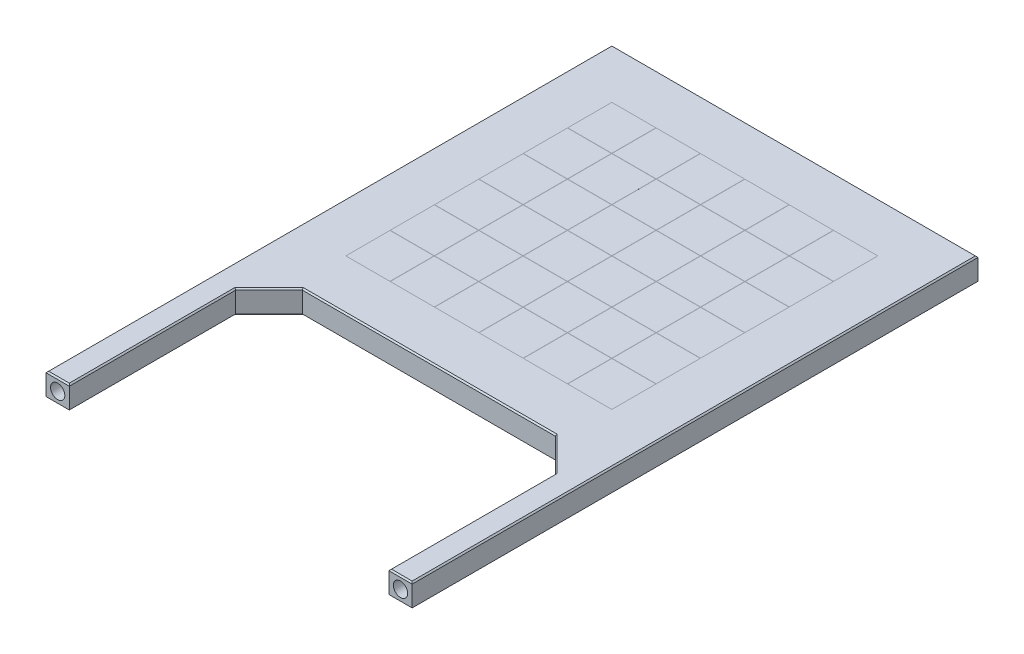
SolidWorks part; units mm, degrees
note: The reader was unsure of these and kept them because the rebuilt part matched: shared geometry of "Sketch7<2>", "Sketch7<3>", "Sketch7<4>".
ref_plane "Front Plane" through (0, 0, 0) normal (0, 0, 1) x (1, 0, 0)
ref_plane "Top Plane" through (0, 0, 0) normal (0, 1, 0) x (1, 0, 0)
ref_plane "Right Plane" through (0, 0, 0) normal (1, 0, 0) x (0, 0, -1)
sketch "Sketch1" plane through (0, 0, 0) normal (0, 1, 0) x (1, 0, 0)
  line L1 (-55, -55) -> (55, -55)
  line L2 (-55, -55) -> (-55, 55)
  line L3 (-55, 55) -> (55, 55)
  line L4 (55, -55) -> (55, 55)
  line L5 (-55, -55) -> (55, 55) construction
  line L6 (-55, 55) -> (55, -55) construction
  point P0 (0, 0)
  dimension "D1" = 110
extrude "Boss-Extrude1" add sketch "Sketch1" along normal blind 7
sketch "Sketch2" plane through (0, 7, 0) normal (0, 1, 0) x (1, 0, 0)
  line L1 (-55, -55) -> (-48, -55)
  line L2 (-55, -55) -> (-55, -115)
  line L3 (-55, -115) -> (-48, -115)
  line L4 (-48, -55) -> (-48, -115)
  line L5 (55, -55) -> (48, -55)
  line L6 (55, -55) -> (55, -115)
  line L7 (55, -115) -> (48, -115)
  line L8 (48, -55) -> (48, -115)
  dimension "D1" = 7
  dimension "D2" = 60
extrude "Boss-Extrude3" add sketch "Sketch2" against normal up to surface (7 mm away) up to face at (0, 0, 0)
sketch "Sketch4" plane through (0, 0, 115) normal (0, 0, 1) x (1, 0, 0)
  line L0 (-48, 7) -> (-55, 0) construction
  line L1 (48, 7) -> (55, 0) construction
  circle A0 centre (-51.5, 3.5) radius 2.15
  circle A1 centre (51.5, 3.5) radius 2.15
  dimension "D1" = 4.3
extrude "Cut-Extrude2" cut sketch "Sketch4" against normal blind 10
sketch "Sketch5" plane through (0, 0, 0) normal (0, -1, 0) x (1, 0, 0)
  line L5 (-40, 40) -> (-26.6667, 40)
  line L6 (-40, 40) -> (-40, 26.6667)
  line L7 (-40, 26.6667) -> (-26.6667, 26.6667)
  line L8 (-26.6667, 40) -> (-26.6667, 26.6667)
  line L9 (-26.6667, 40) -> (-13.3333, 40)
  line L10 (-26.6667, 40) -> (-26.6667, 26.6667)
  line L11 (-26.6667, 26.6667) -> (-13.3333, 26.6667)
  line L12 (-13.3333, 40) -> (-13.3333, 26.6667)
  line L13 (-13.3333, 40) -> (0, 40)
  line L14 (-13.3333, 40) -> (-13.3333, 26.6667)
  line L15 (-13.3333, 26.6667) -> (0, 26.6667)
  line L16 (0, 40) -> (0, 26.6667)
  line L17 (0, 40) -> (13.3333, 40)
  line L18 (0, 40) -> (0, 26.6667)
  line L19 (0, 26.6667) -> (13.3333, 26.6667)
  line L20 (13.3333, 40) -> (13.3333, 26.6667)
  line L21 (13.3333, 40) -> (26.6667, 40)
  line L22 (13.3333, 40) -> (13.3333, 26.6667)
  line L23 (13.3333, 26.6667) -> (26.6667, 26.6667)
  line L24 (26.6667, 40) -> (26.6667, 26.6667)
  line L25 (26.6667, 40) -> (40, 40)
  line L26 (26.6667, 40) -> (26.6667, 26.6667)
  line L27 (26.6667, 26.6667) -> (40, 26.6667)
  line L28 (40, 40) -> (40, 26.6667)
  line L29 (-26.6667, 26.6667) -> (-40, 26.6667)
  line L30 (-26.6667, 26.6667) -> (-26.6667, 13.3333)
  line L31 (-26.6667, 13.3333) -> (-40, 13.3333)
  line L32 (-40, 26.6667) -> (-40, 13.3333)
  line L33 (-26.6667, 26.6667) -> (-13.3333, 26.6667)
  line L34 (-26.6667, 26.6667) -> (-26.6667, 13.3333)
  line L35 (-26.6667, 13.3333) -> (-13.3333, 13.3333)
  line L36 (-13.3333, 26.6667) -> (-13.3333, 13.3333)
  line L37 (-13.3333, 13.3333) -> (0, 13.3333)
  line L38 (-13.3333, 13.3333) -> (-13.3333, 26.6667)
  line L39 (-13.3333, 26.6667) -> (0, 26.6667)
  line L40 (0, 13.3333) -> (0, 26.6667)
  line L41 (0, 13.3333) -> (13.3333, 13.3333)
  line L42 (0, 13.3333) -> (0, 26.6667)
  line L43 (0, 26.6667) -> (13.3333, 26.6667)
  line L44 (13.3333, 13.3333) -> (13.3333, 26.6667)
  line L45 (13.3333, 13.3333) -> (26.6667, 13.3333)
  line L46 (13.3333, 13.3333) -> (13.3333, 26.6667)
  line L47 (13.3333, 26.6667) -> (26.6667, 26.6667)
  line L48 (26.6667, 13.3333) -> (26.6667, 26.6667)
  line L49 (26.6667, 13.3333) -> (40, 13.3333)
  line L50 (26.6667, 13.3333) -> (26.6667, 26.6667)
  line L51 (26.6667, 26.6667) -> (40, 26.6667)
  line L52 (40, 13.3333) -> (40, 26.6667)
  line L53 (-40, 13.3333) -> (-26.6667, 13.3333)
  line L54 (-40, 13.3333) -> (-40, 0)
  line L55 (-40, 0) -> (-26.6667, 0)
  line L56 (-26.6667, 13.3333) -> (-26.6667, 0)
  line L57 (-26.6667, 0) -> (-13.3333, 0)
  line L58 (-26.6667, 0) -> (-26.6667, 13.3333)
  line L59 (-26.6667, 13.3333) -> (-13.3333, 13.3333)
  line L60 (-13.3333, 0) -> (-13.3333, 13.3333)
  line L61 (-13.3333, 0) -> (0, 0)
  line L62 (-13.3333, 0) -> (-13.3333, 13.3333)
  line L63 (-13.3333, 13.3333) -> (0, 13.3333)
  line L64 (0, 0) -> (0, 13.3333)
  line L65 (0, 0) -> (13.3333, 0)
  line L66 (0, 0) -> (0, 13.3333)
  line L67 (0, 13.3333) -> (13.3333, 13.3333)
  line L68 (13.3333, 0) -> (13.3333, 13.3333)
  line L69 (13.3333, 0) -> (26.6667, 0)
  line L70 (13.3333, 0) -> (13.3333, 13.3333)
  line L71 (13.3333, 13.3333) -> (26.6667, 13.3333)
  line L72 (26.6667, 0) -> (26.6667, 13.3333)
  line L73 (26.6667, 0) -> (40, 0)
  line L74 (26.6667, 0) -> (26.6667, 13.3333)
  line L75 (26.6667, 13.3333) -> (40, 13.3333)
  line L76 (40, 0) -> (40, 13.3333)
  line L77 (-40, 0) -> (-26.6667, 0)
  line L78 (-40, 0) -> (-40, -13.3333)
  line L79 (-40, -13.3333) -> (-26.6667, -13.3333)
  line L80 (-26.6667, 0) -> (-26.6667, -13.3333)
  line L81 (-26.6667, -13.3333) -> (-13.3333, -13.3333)
  line L82 (-26.6667, -13.3333) -> (-26.6667, 0)
  line L83 (-26.6667, 0) -> (-13.3333, 0)
  line L84 (-13.3333, -13.3333) -> (-13.3333, 0)
  line L85 (-13.3333, -13.3333) -> (0, -13.3333)
  line L86 (-13.3333, -13.3333) -> (-13.3333, 0)
  line L87 (-13.3333, 0) -> (0, 0)
  line L88 (0, -13.3333) -> (0, 0)
  line L89 (0, -13.3333) -> (13.3333, -13.3333)
  line L90 (0, -13.3333) -> (0, 0)
  line L91 (0, 0) -> (13.3333, 0)
  line L92 (13.3333, -13.3333) -> (13.3333, 0)
  line L93 (13.3333, -13.3333) -> (26.6667, -13.3333)
  line L94 (13.3333, -13.3333) -> (13.3333, 0)
  line L95 (13.3333, 0) -> (26.6667, 0)
  line L96 (26.6667, -13.3333) -> (26.6667, 0)
  line L97 (26.6667, -13.3333) -> (40, -13.3333)
  line L98 (26.6667, -13.3333) -> (26.6667, 0)
  line L99 (26.6667, 0) -> (40, 0)
  line L100 (40, -13.3333) -> (40, 0)
  line L101 (-40, -13.3333) -> (-26.6667, -13.3333)
  line L102 (-40, -13.3333) -> (-40, -26.6667)
  line L103 (-40, -26.6667) -> (-26.6667, -26.6667)
  line L104 (-26.6667, -13.3333) -> (-26.6667, -26.6667)
  line L105 (-26.6667, -26.6667) -> (-13.3333, -26.6667)
  line L106 (-26.6667, -26.6667) -> (-26.6667, -13.3333)
  line L107 (-26.6667, -13.3333) -> (-13.3333, -13.3333)
  line L108 (-13.3333, -26.6667) -> (-13.3333, -13.3333)
  line L109 (-13.3333, -26.6667) -> (0, -26.6667)
  line L110 (-13.3333, -26.6667) -> (-13.3333, -13.3333)
  line L111 (-13.3333, -13.3333) -> (0, -13.3333)
  line L112 (0, -26.6667) -> (0, -13.3333)
  line L113 (0, -26.6667) -> (13.3333, -26.6667)
  line L114 (0, -26.6667) -> (0, -13.3333)
  line L115 (0, -13.3333) -> (13.3333, -13.3333)
  line L116 (13.3333, -26.6667) -> (13.3333, -13.3333)
  line L117 (13.3333, -26.6667) -> (26.6667, -26.6667)
  line L118 (13.3333, -26.6667) -> (13.3333, -13.3333)
  line L119 (13.3333, -13.3333) -> (26.6667, -13.3333)
  line L120 (26.6667, -26.6667) -> (26.6667, -13.3333)
  line L121 (26.6667, -26.6667) -> (40, -26.6667)
  line L122 (26.6667, -26.6667) -> (26.6667, -13.3333)
  line L123 (26.6667, -13.3333) -> (40, -13.3333)
  line L124 (40, -26.6667) -> (40, -13.3333)
  line L125 (-40, -26.6667) -> (-26.6667, -26.6667)
  line L126 (-40, -26.6667) -> (-40, -40)
  line L127 (-40, -40) -> (-26.6667, -40)
  line L128 (-26.6667, -26.6667) -> (-26.6667, -40)
  line L129 (-26.6667, -40) -> (-13.3333, -40)
  line L130 (-26.6667, -40) -> (-26.6667, -26.6667)
  line L131 (-26.6667, -26.6667) -> (-13.3333, -26.6667)
  line L132 (-13.3333, -40) -> (-13.3333, -26.6667)
  line L133 (-13.3333, -40) -> (0, -40)
  line L134 (-13.3333, -40) -> (-13.3333, -26.6667)
  line L135 (-13.3333, -26.6667) -> (0, -26.6667)
  line L136 (0, -40) -> (0, -26.6667)
  line L137 (0, -40) -> (13.3333, -40)
  line L138 (0, -40) -> (0, -26.6667)
  line L139 (0, -26.6667) -> (13.3333, -26.6667)
  line L140 (13.3333, -40) -> (13.3333, -26.6667)
  line L141 (13.3333, -40) -> (26.6667, -40)
  line L142 (13.3333, -40) -> (13.3333, -26.6667)
  line L143 (13.3333, -26.6667) -> (26.6667, -26.6667)
  line L144 (26.6667, -40) -> (26.6667, -26.6667)
  line L145 (26.6667, -40) -> (40, -40)
  line L146 (26.6667, -40) -> (26.6667, -26.6667)
  line L147 (26.6667, -26.6667) -> (40, -26.6667)
  line L148 (40, -40) -> (40, -26.6667)
  dimension "D1" = 80
sketch "Sketch7" plane through (0, 0, 0) normal (0, -1, 0) x (1, 0, 0)
  line L9 (-13.3767, 39.96) -> (-26.63, 39.96)
  line L10 (-26.63, 39.96) -> (-26.63, 26.7067)
  line L11 (-26.63, 26.7067) -> (-13.3767, 26.7067)
  line L12 (-13.3767, 26.7067) -> (-13.3767, 39.96)
  line L13 (-26.7067, 39.96) -> (-39.96, 39.96)
  line L14 (-26.7067, 26.7067) -> (-26.7067, 39.96)
  line L15 (-39.96, 26.7067) -> (-26.7067, 26.7067)
  line L16 (-39.96, 39.96) -> (-39.96, 26.7067)
  line L17 (-26.7067, 39.96) -> (-39.96, 39.96)
  line L18 (-26.7067, 26.7067) -> (-26.7067, 39.96)
  line L19 (-39.96, 26.7067) -> (-26.7067, 26.7067)
  line L20 (-39.96, 39.96) -> (-39.96, 26.7067)
  line L21 (-0.0467, 39.96) -> (-13.3, 39.96)
  line L22 (-13.3, 39.96) -> (-13.3, 26.7067)
  line L23 (-13.3, 26.7067) -> (-0.0467, 26.7067)
  line L24 (-0.0467, 26.7067) -> (-0.0467, 39.96)
  line L25 (13.2833, 39.96) -> (0.03, 39.96)
  line L26 (0.03, 39.96) -> (0.03, 26.7067)
  line L27 (0.03, 26.7067) -> (13.2833, 26.7067)
  line L28 (13.2833, 26.7067) -> (13.2833, 39.96)
  line L29 (26.6133, 39.96) -> (13.36, 39.96)
  line L30 (13.36, 39.96) -> (13.36, 26.7067)
  line L31 (13.36, 26.7067) -> (26.6133, 26.7067)
  line L32 (26.6133, 26.7067) -> (26.6133, 39.96)
  line L33 (39.9433, 39.96) -> (26.69, 39.96)
  line L34 (26.69, 39.96) -> (26.69, 26.7067)
  line L35 (26.69, 26.7067) -> (39.9433, 26.7067)
  line L36 (39.9433, 26.7067) -> (39.9433, 39.96)
  line L37 (-13.3767, 26.63) -> (-26.63, 26.63)
  line L38 (-26.63, 26.63) -> (-26.63, 13.3767)
  line L39 (-26.63, 13.3767) -> (-13.3767, 13.3767)
  line L40 (-13.3767, 13.3767) -> (-13.3767, 26.63)
  line L41 (-0.0467, 26.63) -> (-13.3, 26.63)
  line L42 (-13.3, 26.63) -> (-13.3, 13.3767)
  line L43 (-13.3, 13.3767) -> (-0.0467, 13.3767)
  line L44 (-0.0467, 13.3767) -> (-0.0467, 26.63)
  line L45 (13.2833, 26.63) -> (0.03, 26.63)
  line L46 (0.03, 26.63) -> (0.03, 13.3767)
  line L47 (0.03, 13.3767) -> (13.2833, 13.3767)
  line L48 (13.2833, 13.3767) -> (13.2833, 26.63)
  line L49 (26.6133, 26.63) -> (13.36, 26.63)
  line L50 (13.36, 26.63) -> (13.36, 13.3767)
  line L51 (13.36, 13.3767) -> (26.6133, 13.3767)
  line L52 (26.6133, 13.3767) -> (26.6133, 26.63)
  line L53 (39.9433, 26.63) -> (26.69, 26.63)
  line L54 (26.69, 26.63) -> (26.69, 13.3767)
  line L55 (26.69, 13.3767) -> (39.9433, 13.3767)
  line L56 (39.9433, 13.3767) -> (39.9433, 26.63)
  line L57 (-13.3767, 13.3) -> (-26.63, 13.3)
  line L58 (-26.63, 13.3) -> (-26.63, 0.0467)
  line L59 (-26.63, 0.0467) -> (-13.3767, 0.0467)
  line L60 (-13.3767, 0.0467) -> (-13.3767, 13.3)
  line L61 (-0.0467, 13.3) -> (-13.3, 13.3)
  line L62 (-13.3, 13.3) -> (-13.3, 0.0467)
  line L63 (-13.3, 0.0467) -> (-0.0467, 0.0467)
  line L64 (-0.0467, 0.0467) -> (-0.0467, 13.3)
  line L65 (13.2833, 13.3) -> (0.03, 13.3)
  line L66 (0.03, 13.3) -> (0.03, 0.0467)
  line L67 (0.03, 0.0467) -> (13.2833, 0.0467)
  line L68 (13.2833, 0.0467) -> (13.2833, 13.3)
  line L69 (26.6133, 13.3) -> (13.36, 13.3)
  line L70 (13.36, 13.3) -> (13.36, 0.0467)
  line L71 (13.36, 0.0467) -> (26.6133, 0.0467)
  line L72 (26.6133, 0.0467) -> (26.6133, 13.3)
  line L73 (39.9433, 13.3) -> (26.69, 13.3)
  line L74 (26.69, 13.3) -> (26.69, 0.0467)
  line L75 (26.69, 0.0467) -> (39.9433, 0.0467)
  line L76 (39.9433, 0.0467) -> (39.9433, 13.3)
  line L77 (-13.3767, -0.03) -> (-26.63, -0.03)
  line L78 (-26.63, -0.03) -> (-26.63, -13.2833)
  line L79 (-26.63, -13.2833) -> (-13.3767, -13.2833)
  line L80 (-13.3767, -13.2833) -> (-13.3767, -0.03)
  line L81 (-0.0467, -0.03) -> (-13.3, -0.03)
  line L82 (-13.3, -0.03) -> (-13.3, -13.2833)
  line L83 (-13.3, -13.2833) -> (-0.0467, -13.2833)
  line L84 (-0.0467, -13.2833) -> (-0.0467, -0.03)
  line L85 (13.2833, -0.03) -> (0.03, -0.03)
  line L86 (0.03, -0.03) -> (0.03, -13.2833)
  line L87 (0.03, -13.2833) -> (13.2833, -13.2833)
  line L88 (13.2833, -13.2833) -> (13.2833, -0.03)
  line L89 (26.6133, -0.03) -> (13.36, -0.03)
  line L90 (13.36, -0.03) -> (13.36, -13.2833)
  line L91 (13.36, -13.2833) -> (26.6133, -13.2833)
  line L92 (26.6133, -13.2833) -> (26.6133, -0.03)
  line L93 (39.9433, -0.03) -> (26.69, -0.03)
  line L94 (26.69, -0.03) -> (26.69, -13.2833)
  line L95 (26.69, -13.2833) -> (39.9433, -13.2833)
  line L96 (39.9433, -13.2833) -> (39.9433, -0.03)
  line L97 (-13.3767, -13.36) -> (-26.63, -13.36)
  line L98 (-26.63, -13.36) -> (-26.63, -26.6133)
  line L99 (-26.63, -26.6133) -> (-13.3767, -26.6133)
  line L100 (-13.3767, -26.6133) -> (-13.3767, -13.36)
  line L101 (-0.0467, -13.36) -> (-13.3, -13.36)
  line L102 (-13.3, -13.36) -> (-13.3, -26.6133)
  line L103 (-13.3, -26.6133) -> (-0.0467, -26.6133)
  line L104 (-0.0467, -26.6133) -> (-0.0467, -13.36)
  line L105 (13.2833, -13.36) -> (0.03, -13.36)
  line L106 (0.03, -13.36) -> (0.03, -26.6133)
  line L107 (0.03, -26.6133) -> (13.2833, -26.6133)
  line L108 (13.2833, -26.6133) -> (13.2833, -13.36)
  line L109 (26.6133, -13.36) -> (13.36, -13.36)
  line L110 (13.36, -13.36) -> (13.36, -26.6133)
  line L111 (13.36, -26.6133) -> (26.6133, -26.6133)
  line L112 (26.6133, -26.6133) -> (26.6133, -13.36)
  line L113 (39.9433, -13.36) -> (26.69, -13.36)
  line L114 (26.69, -13.36) -> (26.69, -26.6133)
  line L115 (26.69, -26.6133) -> (39.9433, -26.6133)
  line L116 (39.9433, -26.6133) -> (39.9433, -13.36)
  line L117 (-13.3767, -26.69) -> (-26.63, -26.69)
  line L118 (-26.63, -26.69) -> (-26.63, -39.9433)
  line L119 (-26.63, -39.9433) -> (-13.3767, -39.9433)
  line L120 (-13.3767, -39.9433) -> (-13.3767, -26.69)
  line L121 (-0.0467, -26.69) -> (-13.3, -26.69)
  line L122 (-13.3, -26.69) -> (-13.3, -39.9433)
  line L123 (-13.3, -39.9433) -> (-0.0467, -39.9433)
  line L124 (-0.0467, -39.9433) -> (-0.0467, -26.69)
  line L125 (13.2833, -26.69) -> (0.03, -26.69)
  line L126 (0.03, -26.69) -> (0.03, -39.9433)
  line L127 (0.03, -39.9433) -> (13.2833, -39.9433)
  line L128 (13.2833, -39.9433) -> (13.2833, -26.69)
  line L129 (26.6133, -26.69) -> (13.36, -26.69)
  line L130 (13.36, -26.69) -> (13.36, -39.9433)
  line L131 (13.36, -39.9433) -> (26.6133, -39.9433)
  line L132 (26.6133, -39.9433) -> (26.6133, -26.69)
  line L133 (39.9433, -26.69) -> (26.69, -26.69)
  line L134 (26.69, -26.69) -> (26.69, -39.9433)
  line L135 (26.69, -39.9433) -> (39.9433, -39.9433)
  line L136 (39.9433, -39.9433) -> (39.9433, -26.69)
  line L137 (-26.7067, 26.63) -> (-39.96, 26.63)
  line L138 (-39.96, 26.63) -> (-39.96, 13.3767)
  line L139 (-39.96, 13.3767) -> (-26.7067, 13.3767)
  line L140 (-26.7067, 13.3767) -> (-26.7067, 26.63)
  line L141 (-26.7067, 13.3) -> (-39.96, 13.3)
  line L142 (-39.96, 13.3) -> (-39.96, 0.0467)
  line L143 (-39.96, 0.0467) -> (-26.7067, 0.0467)
  line L144 (-26.7067, 0.0467) -> (-26.7067, 13.3)
  line L145 (-26.7067, -0.03) -> (-39.96, -0.03)
  line L146 (-39.96, -0.03) -> (-39.96, -13.2833)
  line L147 (-39.96, -13.2833) -> (-26.7067, -13.2833)
  line L148 (-26.7067, -13.2833) -> (-26.7067, -0.03)
  line L149 (-26.7067, -13.36) -> (-39.96, -13.36)
  line L150 (-39.96, -13.36) -> (-39.96, -26.6133)
  line L151 (-39.96, -26.6133) -> (-26.7067, -26.6133)
  line L152 (-26.7067, -26.6133) -> (-26.7067, -13.36)
  line L153 (-26.7067, -26.69) -> (-39.96, -26.69)
  line L154 (-39.96, -26.69) -> (-39.96, -39.9433)
  line L155 (-39.96, -39.9433) -> (-26.7067, -39.9433)
  line L156 (-26.7067, -39.9433) -> (-26.7067, -26.69)
  dimension "D1" = 0.04
  dimension "D2" = 6
  dimension "D3" = 6
extrude "Cut-Extrude3" cut sketch "Sketch7" against normal blind 1
extrude "Boss-Extrude4" add sketch "Sketch7<2>" against normal up to surface (1 mm away) separate body up to face at (-20.0033, 1, 6.6733)
sketch "Sketch7<2>" plane through (0, 0, 0) normal (0, -1, 0) x (1, 0, 0) same geometry as "Sketch7"
extrude "Cut-Extrude4" cut sketch "Sketch7<3>" along normal blind 1 from surface at -7 starting at face at (0, 7, 57.5)
sketch "Sketch7<3>" plane through (0, 0, 0) normal (0, -1, 0) x (1, 0, 0) same geometry as "Sketch7"
extrude "Boss-Extrude5" add sketch "Sketch7<4>" along normal up to surface (1 mm away) from surface at -7 separate body up to face at (-20.0033, 6, -19.9867) starting at face at (6.6567, 7, -6.6567)
sketch "Sketch7<4>" plane through (0, 0, 0) normal (0, -1, 0) x (1, 0, 0) same geometry as "Sketch7"
chamfer "Chamfer1" distance 10 angle 45 2 edges at (-48, 3.5, 55) (48, 3.5, 55)
chamfer "Chamfer2" distance 0.4 angle 45 20 edges at (51.5, 0, 115) (51.5, 7, 115) (48, 7, 90) (48, 0, 90) (43, 7, 60) (0, 7, 55) (-43, 7, 60) (-48, 0, 90) (-48, 7, 90) (-51.5, 0, 115) (-51.5, 7, 115) (-55, 7, 30) (-55, 0, 30) (-43, 0, 60) (0, 0, 55) (43, 0, 60) (55, 7, 30) (0, 7, -55) (55, 0, 30) (0, 0, -55)
